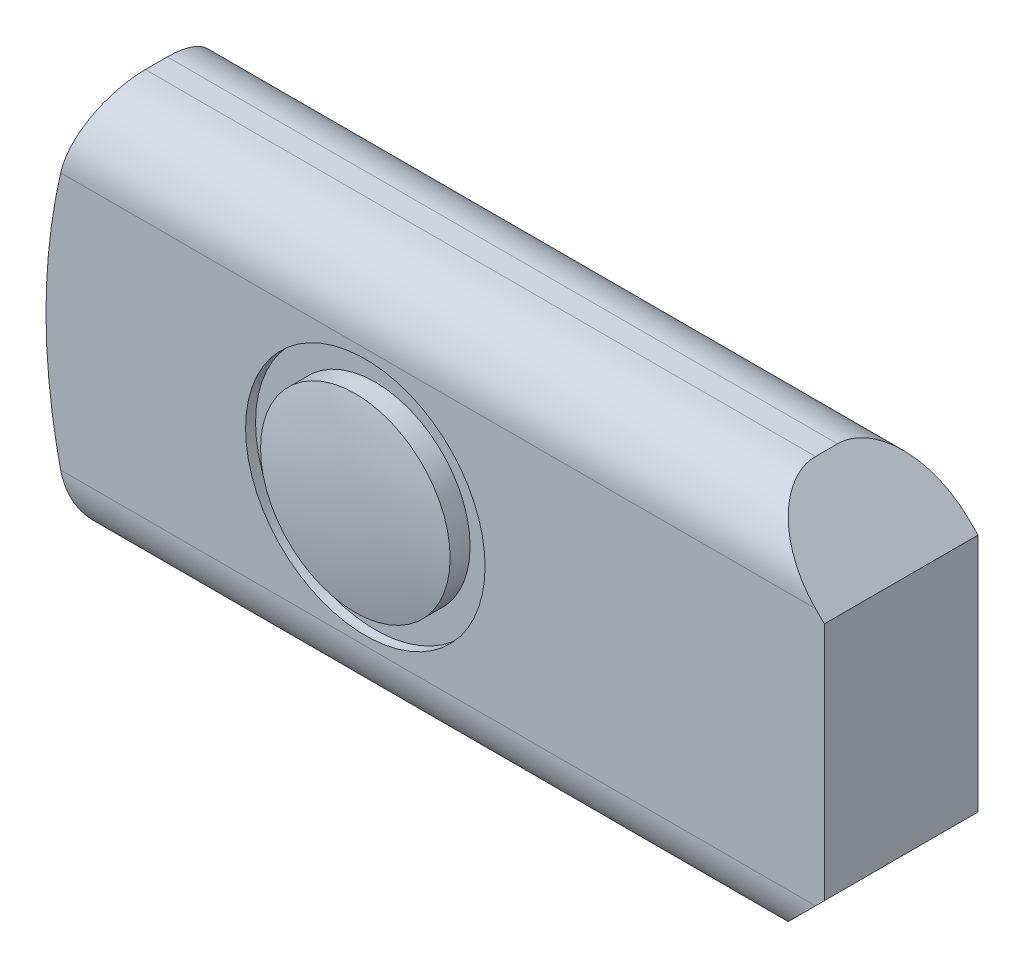
SolidWorks part; units mm, degrees
ref_plane "Front Plane" through (0, 0, 0) normal (0, 0, 1) x (1, 0, 0)
ref_plane "Top Plane" through (0, 0, 0) normal (0, 1, 0) x (1, 0, 0)
ref_plane "Right Plane" through (0, 0, 0) normal (1, 0, 0) x (0, 0, -1)
sketch "Sketch1" plane through (0, 0, 0) normal (0, 0, 1) x (1, 0, 0)
  line L0 (1.6786, 0) -> (1.6786, 29.1144) construction
  line L1 (1.6786, 0) -> (39, 0)
  line L3 (1.6786, 19.5) -> (39, 19.5)
  line L4 (39, 0) -> (39, 19.5)
  spline S0 degree 2 poles (1.6786, 19.5) (-1.6786, 9.75) (1.6786, 0) knots 0 0 0 1 1 1
  dimension "D1" = 19.5
extrude "Boss-Extrude1" add sketch "Sketch1" along normal blind 7.7 contours L3 L4 L1 S0
fillet "Fillet1" radius 3.3 4 edges at (20.3393, 0, 7.7) (20.3393, 0, 0) (20.3393, 19.5, 0) (20.3393, 19.5, 7.7)
sketch "Sketch2" plane through (0, 0, 0) normal (0, 0, 1) x (1, 0, 0)
  line L0 (35.2582, 19.5) -> (39, 15.7582)
  line L1 (39, 15.7582) -> (39, 3.7418)
  line L2 (39, 3.7418) -> (35.2582, 0)
  line L3 (35.2582, 0) -> (41.5465, 0)
  line L4 (41.5465, 0) -> (41.5465, 19.5)
  line L5 (41.5465, 19.5) -> (35.2582, 19.5)
  line L6 (39, 3.3) -> (39, 16.2) construction
  line L7 (1.6786, 19.5) -> (39, 19.5) construction
  dimension "D1" = 45
  dimension "D2" = 45
  dimension "D3" = 19.5
  dimension "D4" = 0
extrude "Cut-Extrude1" cut sketch "Sketch2" along normal blind 14.5
fillet "Fillet2" [suppressed] radius 0.5
sketch "Sketch3" plane through (0, 0, 7.7) normal (0, 0, 1) x (1, 0, 0)
  line L0 (39, 9.75) -> (-4.542, 9.75) construction
  line L1 (39, 3.7418) -> (39, 15.7582) construction
  circle A0 centre (16, 9.75) radius 4.75
  dimension "D1" = 9.5
  dimension "D2" = 23
extrude "Boss-Extrude2" add sketch "Sketch3" along normal blind 0.5 and the other way blind 8.2
dome "Dome1" faces to dome 1 distance 0.5 reverse direction no elliptical dome no face at (20.75, 9.75, 8.2) parameters "D1"=0.5
dome "Dome2" faces to dome 1 distance 0.5 reverse direction no elliptical dome no face at (20.75, 9.75, -0.5) parameters "D1"=0.5
sketch "Sketch4" plane through (0, 0, 0) normal (0, 0, -1) x (-1, 0, 0)
  circle A0 centre (-16, 9.75) radius 6
  circle A1 centre (-16, 9.75) radius 4.75
extrude "Cut-Extrude2" cut sketch "Sketch4" against normal blind 0.5
sketch "Sketch5" plane through (0, 0, 7.7) normal (0, 0, 1) x (1, 0, 0)
  circle A0 centre (16, 9.75) radius 6
  circle A1 centre (16, 9.75) radius 4.75
extrude "Cut-Extrude3" cut sketch "Sketch5" against normal blind 0.5
